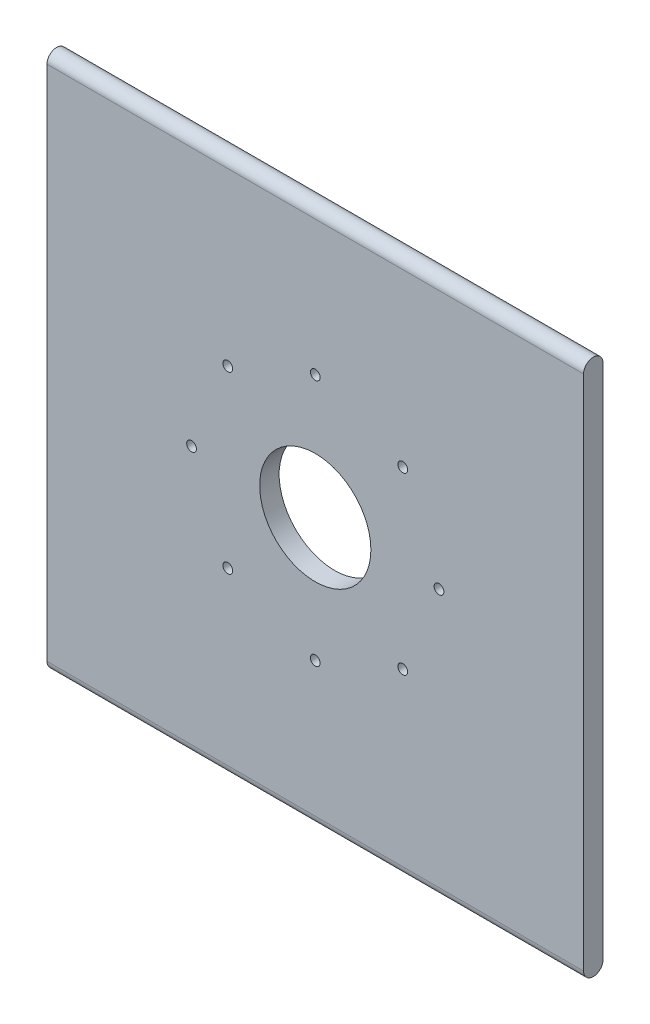
SolidWorks part; units mm, degrees
ref_plane "前视基准面" through (0, 0, 0) normal (0, 0, 1) x (1, 0, 0)
ref_plane "上视基准面" through (0, 0, 0) normal (0, 1, 0) x (1, 0, 0)
ref_plane "右视基准面" through (0, 0, 0) normal (1, 0, 0) x (0, 0, -1)
sketch "草图1" plane through (0, 0, 0) normal (0, 0, 1) x (1, 0, 0)
  line L1 (-96.5, 96.5) -> (96.5, 96.5)
  line L2 (-96.5, 96.5) -> (-96.5, -96.5)
  line L3 (-96.5, -96.5) -> (96.5, -96.5)
  line L4 (96.5, 96.5) -> (96.5, -96.5)
  line L5 (-96.5, 96.5) -> (96.5, -96.5) construction
  line L6 (-96.5, -96.5) -> (96.5, 96.5) construction
  point P0 (0, 0)
  dimension "D1" = 193
  dimension "D2" = 193
extrude "凸台-拉伸1" add sketch "草图1" along normal blind 7
sketch "草图2" plane through (0, 0, 7) normal (0, 0, 1) x (1, 0, 0)
  circle A0 centre (0, 0) radius 20
extrude "切除-拉伸1" cut sketch "草图2" against normal blind 123
sketch "草图3" plane through (0, 0, 7) normal (0, 0, 1) x (1, 0, 0)
  circle A0 centre (0, 0) radius 44.5 construction
  circle A1 centre (0, 44.5) radius 1.75
  circle A2 centre (31.4663, 31.4663) radius 1.75
  circle A3 centre (44.5, 0) radius 1.75
  circle A4 centre (31.4663, -31.4663) radius 1.75
  circle A5 centre (0, -44.5) radius 1.75
  circle A6 centre (-31.4663, -31.4663) radius 1.75
  circle A7 centre (-44.5, 0) radius 1.75
  circle A8 centre (-31.4663, 31.4663) radius 1.75
  point P21 (0, 0)
  dimension "D1" = 3.5
  dimension "D2" = 8
extrude "切除-拉伸2" cut sketch "草图3" against normal through all contours A5 | A4 | A3 | A2 | A1 | A7 | A6 | A8
fillet "圆角2" 2 edges at (0, 96.5, 0) (0, 96.5, 7) type full round first side face at (1.75, -44.5, 0) second side face at (1.75, -44.5, 7) middle face at (0, 96.5, 3.5)
fillet "圆角4" 2 edges at (0, -96.5, 0) (0, -96.5, 7) type full round first side face at (1.75, -44.5, 0) second side face at (1.75, -44.5, 7) middle face at (0, -96.5, 3.5)
